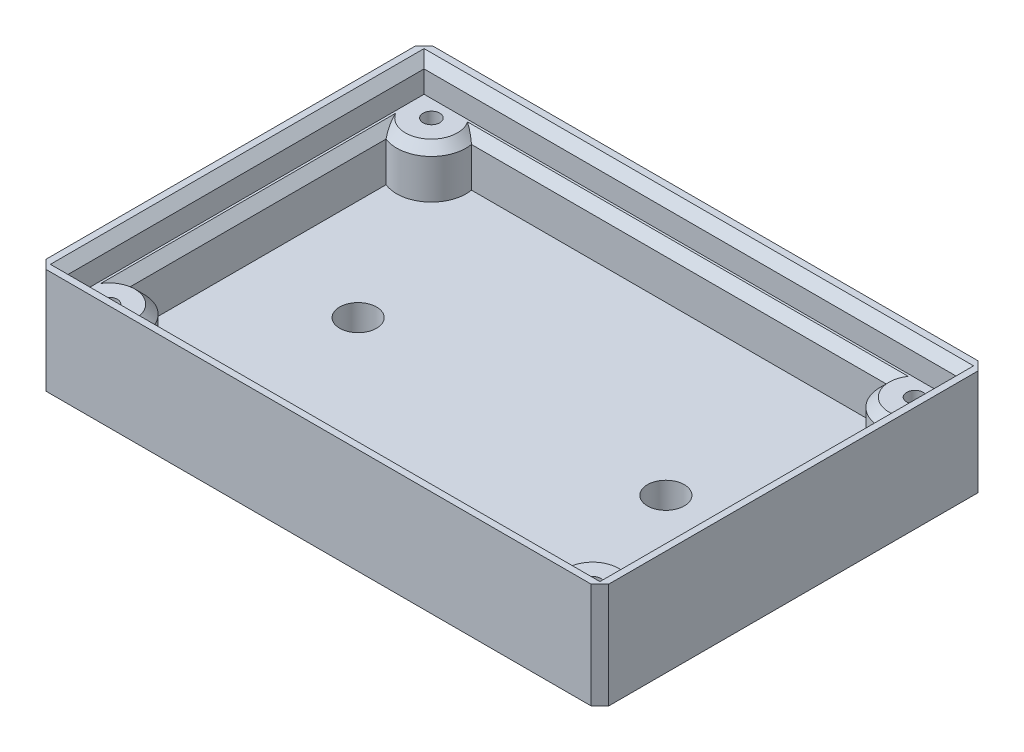
SolidWorks part; units mm, degrees
ref_plane "Front Plane" through (0, 0, 0) normal (0, 0, 1) x (1, 0, 0)
ref_plane "Top Plane" through (0, 0, 0) normal (0, 1, 0) x (1, 0, 0)
ref_plane "Right Plane" through (0, 0, 0) normal (1, 0, 0) x (0, 0, -1)
sketch "Sketch1" plane through (0, 0, 0) normal (0, 1, 0) x (1, 0, 0)
  line L0 (-32, -22) -> (-32, 22)
  line L1 (-30, -20) -> (30, -20) construction
  line L2 (-30, -20) -> (-30, 20) construction
  line L3 (-30, 20) -> (30, 20) construction
  line L4 (30, -20) -> (30, 20) construction
  line L5 (-30, -20) -> (30, 20) construction
  line L6 (-30, 20) -> (30, -20) construction
  line L7 (-32, 22) -> (32, 22)
  line L8 (32, -22) -> (32, 22)
  line L9 (-32, -22) -> (32, -22)
  point P0 (0, 0)
  dimension "D1" = 60
  dimension "D2" = 40
  dimension "D3" = 2
extrude "Boss-Extrude1" add sketch "Sketch1" along normal blind 12
sketch "Sketch2" plane through (0, 12, 0) normal (0, 1, 0) x (1, 0, 0)
  line L1 (-30.25, -20.25) -> (30.25, -20.25)
  line L2 (-30.25, -20.25) -> (-30.25, 20.25)
  line L3 (-30.25, 20.25) -> (30.25, 20.25)
  line L4 (30.25, -20.25) -> (30.25, 20.25)
  line L5 (-30.25, -20.25) -> (30.25, 20.25) construction
  line L6 (-30.25, 20.25) -> (30.25, -20.25) construction
  point P0 (0, 0)
  dimension "D1" = 60.5
  dimension "D2" = 40.5
extrude "Cut-Extrude1" cut sketch "Sketch2" against normal blind 3.5
sketch "Sketch3" plane through (0, 8.5, 0) normal (0, 1, 0) x (1, 0, 0)
  line L1 (30, -20) -> (-30, -20) construction
  line L2 (30, -20) -> (30, 20) construction
  line L3 (30, 20) -> (-30, 20) construction
  line L4 (-30, -20) -> (-30, 20) construction
  line L5 (30, -20) -> (-30, 20) construction
  line L6 (30, 20) -> (-30, -20) construction
  circle A0 centre (-27.5, 18.3333) radius 0.95
  circle A1 centre (27.5, 18.3333) radius 0.95
  circle A2 centre (27.5, -18.3333) radius 0.95
  circle A3 centre (-27.5, -18.3333) radius 0.95
  point P0 (0, 0)
  dimension "D4" = 1.9
  dimension "D1" = 60
  dimension "D2" = 40
  dimension "D3" = 2.5
extrude "Cut-Extrude2" cut sketch "Sketch3" against normal blind 6
shell "Shell1" thickness 3 removed face at (-27.5, 8.5, 19.2833)
chamfer "Chamfer1" distance 1 angle 45 4 edges at (30.25, 12, 0) (0, 12, 20.25) (-30.25, 12, 0) (0, 12, -20.25) tangent propagation no
chamfer "Chamfer2" distance 1 angle 45 8 edges at (0, 8.5, 19) (-25.0303, 8.5, 15.2506) (-29, 8.5, 0) (25.0303, 8.5, 15.2506) (29, 8.5, 0) (25.0303, 8.5, -15.2506) (0, 8.5, -19) (-25.0303, 8.5, -15.2506)
chamfer "Chamfer3" distance 1 angle 45 4 edges at (-32, 6, -22) (32, 6, -22) (32, 6, 22) (-32, 6, 22)
sketch "Sketch4" plane through (0, 3, 0) normal (0, 1, 0) x (1, 0, 0)
  circle A0 centre (-17.5, 0) radius 2.1
  circle A1 centre (17.5, 0) radius 2.1
  dimension "D3" = 4.2
  dimension "D1" = 17.5
  dimension "D2" = 35
extrude "Cut-Extrude3" cut sketch "Sketch4" against normal through all
